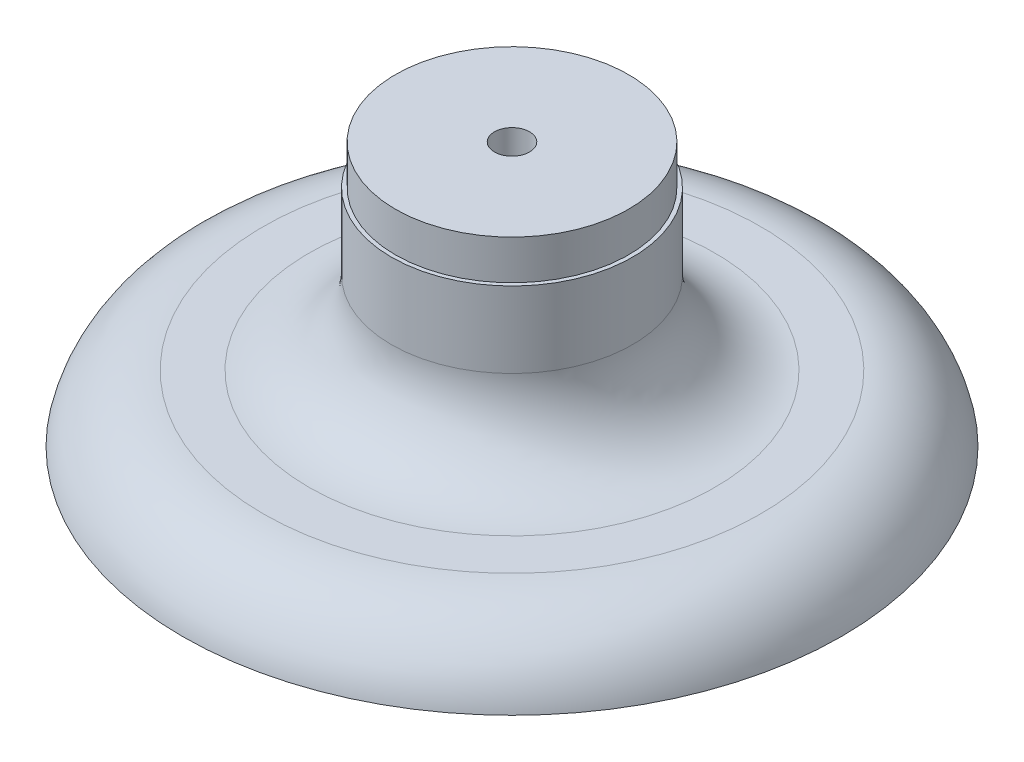
SolidWorks part; units mm, degrees
ref_plane "Front Plane" through (0, 0, 0) normal (0, 0, 1) x (1, 0, 0)
ref_plane "Top Plane" through (0, 0, 0) normal (0, 1, 0) x (1, 0, 0)
ref_plane "Right Plane" through (0, 0, 0) normal (1, 0, 0) x (0, 0, -1)
sketch "Sketch1" plane through (0, 0, 0) normal (0, 1, 0) x (1, 0, 0)
  circle A0 centre (0, 0) radius 22.479
  circle A1 centre (0, 0) radius 23.241
  circle A2 centre (0, 0) radius 63.5
extrude "Boss-Extrude4" add sketch "Sketch1" along normal blind 12.7 contours A2 A1 region at (-61.7039, 0, 0)
extrude "Boss-Extrude5" add sketch "Sketch1<6>" along normal blind 43.18 contours A1 A0 region at (-22.5836, 0, 0)
sketch "Sketch1<6>" plane through (0, 0, 0) normal (0, 1, 0) x (1, 0, 0) same geometry as "Sketch1"
extrude "Boss-Extrude6" add sketch "Sketch1<7>" along normal blind 50.8 contours A0 region at (0, 0, 0)
sketch "Sketch1<7>" plane through (0, 0, 0) normal (0, 1, 0) x (1, 0, 0) same geometry as "Sketch1"
hole_wizard "CSK for 1/4 Flat Head Machine Screw (100)1" positions "Sketch4" profile "Sketch5" countersink size "1/4" standard "ANSI Inch" end condition through all
sketch "Sketch4" plane through (0, 0, 0) normal (0, -1, 0) x (-1, 0, 0)
  point P0 (0, 0)
sketch "Sketch5" plane through (0, 0, 0) normal (1, 0, 0) x (0, 0, -1)
  line L0 (0, 0) -> (0, 50.8)
  line L1 (0, 50.8) -> (3.3782, 50.8)
  line L2 (3.3782, 50.8) -> (3.3782, 2.5682)
  line L3 (3.3782, 2.5682) -> (6.4389, 0)
  line L5 (6.4389, 0) -> (0, 0)
  line L6 (-3.3782, 2.5682) -> (-6.4389, 0) construction
  line L11 (0, -6.35) -> (0, 107.95) construction
  dimension "Thru Hole Dia." = 6.7564
  dimension "Thru Hole Depth" = 50.8
  dimension "Near C'Sink Dia." = 12.8778
  dimension "Near C'Sink Angle" = 100
fillet "Fillet1" radius 15.875 1 edges at (0, 12.7, 23.241)
fillet "Fillet2" radius 15.875 1 edges at (0, 12.7, 63.5)
